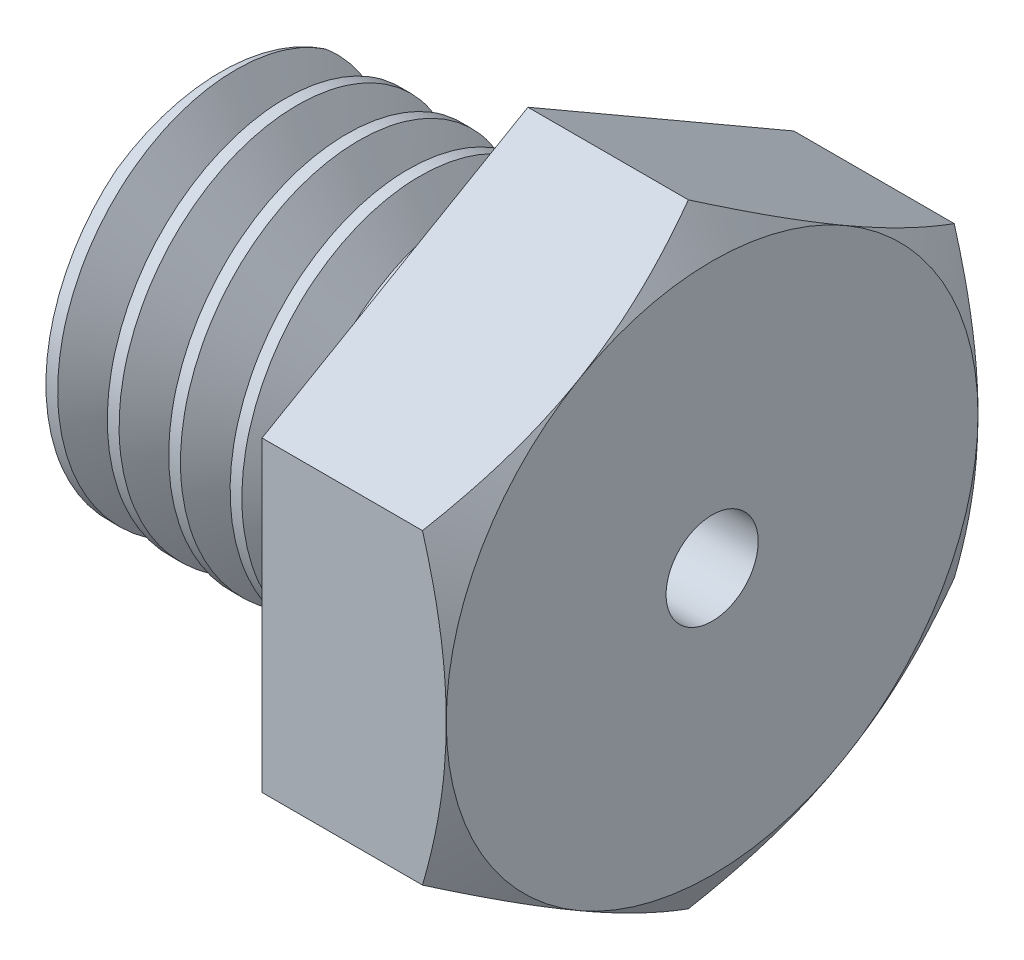
SolidWorks part; units mm, degrees
ref_plane "Front" through (0, 0, 0) normal (0, 0, 1) x (1, 0, 0)
ref_plane "Top" through (0, 0, 0) normal (0, 1, 0) x (1, 0, 0)
ref_plane "Right" through (0, 0, 0) normal (1, 0, 0) x (0, 0, -1)
sketch "Sketch1" plane through (0, 0, 0) normal (1, 0, 0) x (0, 0, -1)
  line L1 (0, 10) -> (-8.6603, 5)
  line L2 (-8.6603, 5) -> (-8.6603, -5)
  line L3 (-8.6603, -5) -> (0, -10)
  line L4 (0, -10) -> (8.6603, -5)
  line L5 (8.6603, -5) -> (8.6603, 5)
  line L6 (8.6603, 5) -> (0, 10)
  circle A0 centre (0, 0) radius 8.6603 construction
  dimension "D1" = 20
extrude "Boss-Extrude1" add sketch "Sketch1" along normal blind 6 contours L1 L2 L3 L4 L5 L6
sketch "Sketch2" plane through (6, 0, 0) normal (1, 0, 0) x (0, 0, -1)
  circle A0 centre (0, 0) radius 8.6603
extrude "Cut-Extrude1" cut sketch "Sketch2" against normal blind 6 draft 60 flip side to cut
sketch "Sketch4" plane through (0, 0, 0) normal (-1, 0, 0) x (0, 0, 1)
  circle A0 centre (0, 0) radius 6
extrude "Boss-Extrude2" add sketch "Sketch4" along normal blind 10
sketch "Sketch5" plane through (-10, 0, 0) normal (-1, 0, 0) x (0, 0, 1)
  circle A0 centre (0, 0) radius 6
curve "Helix/Spiral1" pitch 2 height 10 turns 5
sketch "Sketch6" plane through (0, 0, 0) normal (0, 0, 1) x (1, 0, 0)
  line L1 (-10, -4.6) -> (-11.2124, -6.7)
  line L2 (-11.2124, -6.7) -> (-8.7876, -6.7)
  line L3 (-8.7876, -6.7) -> (-10, -4.6)
  circle A0 centre (-10, -6) radius 0.7 construction
  dimension "D1" = 1.4
sweep "Cut-Sweep1" cut profiles "Sketch6" path "Helix/Spiral1"
sketch "Sketch7" plane through (6, 0, 0) normal (1, 0, 0) x (0, 0, -1)
  circle A0 centre (0, 0) radius 1.5
  dimension "D1" = 3
extrude "Cut-Extrude2" cut sketch "Sketch7" against normal through all
